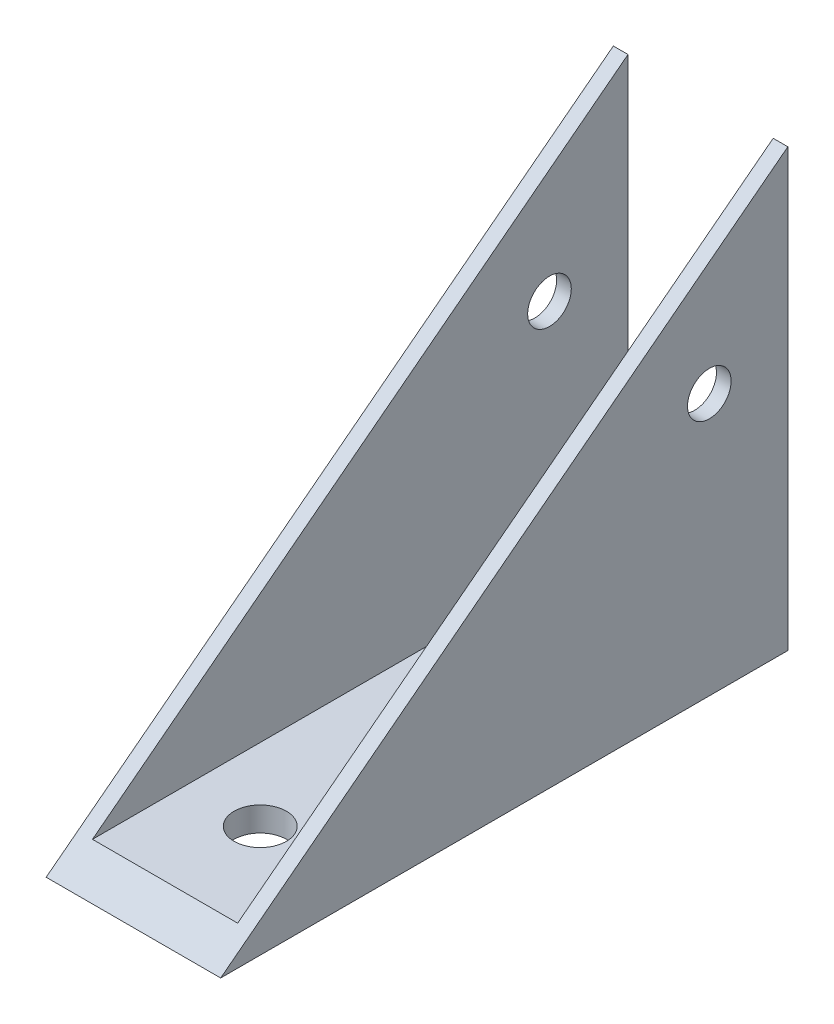
SolidWorks part; units mm, degrees
ref_plane "Front" through (0, 0, 0) normal (0, 0, 1) x (1, 0, 0)
ref_plane "Top" through (0, 0, 0) normal (0, 1, 0) x (1, 0, 0)
ref_plane "Right" through (0, 0, 0) normal (1, 0, 0) x (0, 0, -1)
sketch "Sketch1" plane through (0, 0, 0) normal (1, 0, 0) x (0, 0, -1)
  line L0 (0, 0) -> (65, 0)
  line L1 (65, 0) -> (65, 50)
  line L2 (65, 50) -> (0, 0)
  circle A0 centre (56, 30) radius 2.5
  dimension "D5" = 5
  dimension "D1" = 30
  dimension "D2" = 65
  dimension "D3" = 50
  dimension "D4" = 9
extrude "Boss-Extrude1" add sketch "Sketch1" along normal blind 10 and the other way blind 10
sketch "Sketch2" plane through (0, 0, -65) normal (0, 0, -1) x (-1, 0, 0)
  line L0 (-10, 50) -> (10, 50) construction
  line L1 (-8.3186, 2.7901) -> (-8.3186, 52.8426)
  line L2 (-8.3186, 2.7901) -> (8.3186, 2.7901)
  line L3 (-8.3186, 52.8426) -> (8.3186, 52.8426)
  line L4 (8.3186, 2.7901) -> (8.3186, 52.8426)
  line L5 (-8.3186, 2.7901) -> (8.3186, 52.8426) construction
  line L6 (-8.3186, 52.8426) -> (8.3186, 2.7901) construction
  line L7 (0, 50) -> (0, 19.4596) construction
  point P5 (0, 27.8164)
extrude "Cut-Extrude1" cut sketch "Sketch2" against normal through all
sketch "Sketch5" plane through (0, 2.7901, 0) normal (0, 1, 0) x (1, 0, 0)
  line L0 (0, 65) -> (31, 65) construction
  line L1 (0, 68.6147) -> (0, 61.3853) construction
  line L2 (2.9393, 68.6147) -> (2.9393, 61.3853)
  line L3 (-2.9393, 68.6147) -> (-2.9393, 61.3853)
  line L4 (8.3186, 65) -> (-8.3186, 65) construction
  line L5 (0, 65) -> (0, 0) construction
  arc A0 (2.9393, 68.6147) -> (-2.9393, 68.6147) centre (0, 68.6147) ccw
  arc A1 (-2.9393, 61.3853) -> (2.9393, 61.3853) centre (0, 61.3853) ccw
  circle A2 centre (0, 14.5377) radius 2.9967
  point P6 (0, 65)
  point P13 (0, 14.5377)
  point P16 (0, 65)
extrude "Cut-Extrude2" cut sketch "Sketch5" against normal through all
sketch "Sketch6" plane through (0, 0, 0) normal (1, 0, 0) x (0, 0, -1)
  line L0 (56, 30) -> (56, 0)
  line L2 (0, 0) -> (65, 0) construction
  point P0 (56, 30)
